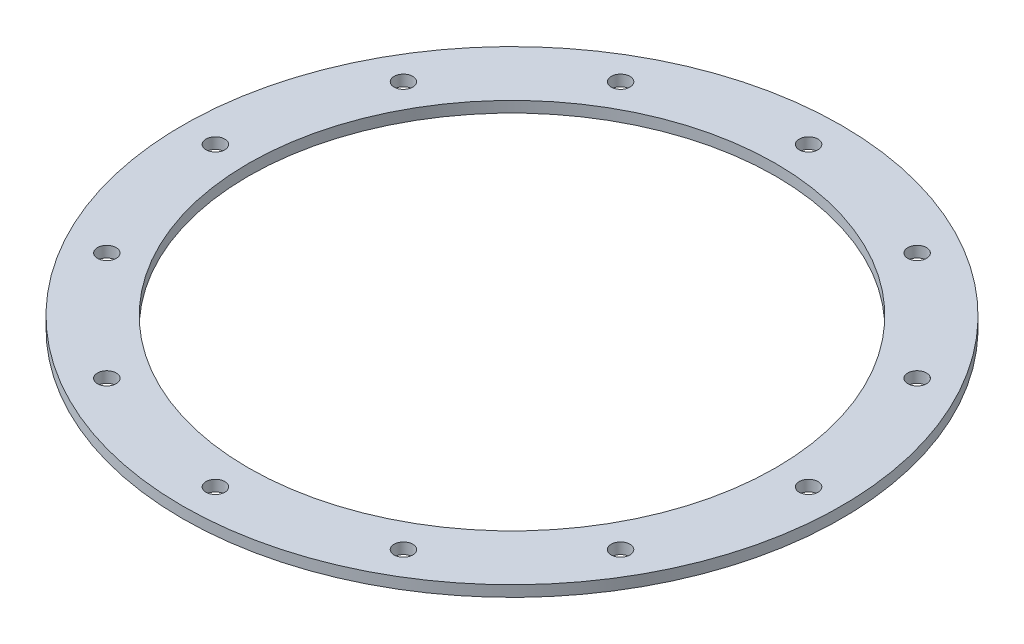
SolidWorks part; units mm, degrees
material "PTFE (general)"
ref_plane "Front Plane" through (0, 0, 0) normal (0, 0, 1) x (1, 0, 0)
ref_plane "Top Plane" through (0, 0, 0) normal (0, 1, 0) x (1, 0, 0)
ref_plane "Right Plane" through (0, 0, 0) normal (1, 0, 0) x (0, 0, -1)
ref_axis "Axis1" through (0, 55, 0) along (0, -1, 0)
sketch "Sketch1" plane through (0, 0, 0) normal (0, 0, 1) x (1, 0, 0)
  line L0 (-38.1, 0) -> (0, 0) construction
  line L1 (-38.1, 0) -> (-47.625, 0)
  line L2 (-38.1, 0) -> (-38.1, 1.5875)
  line L3 (-38.1, 1.5875) -> (-47.625, 1.5875)
  line L4 (-47.625, 0) -> (-47.625, 1.5875)
  line L7 (0, 1.5875) -> (-38.1, 1.5875) construction
  point P12 (-47.625, 0)
  point P18 (-38.1, 1.5875)
revolve "Main" add sketch "Sketch1" angle 360 about axis through (0, 55, 0) along (0, -1, 0)
sketch "Hole Location" plane through (0, 0, 0) normal (0, 1, 0) x (1, 0, 0)
  line L0 (0, 0) -> (-42.8625, 0) construction
  circle A0 centre (0, 0) radius 42.8625 construction
  dimension "D1" = 85.725
hole_wizard "#36 (0.1065) Diameter Hole1" positions "Sketch3" profile "Sketch5" hole size "#36" standard "ANSI Inch" end condition through all
sketch "Sketch3" plane through (0, 0, 0) normal (0, -1, 0) x (-1, 0, 0)
  point P0 (42.8625, 0)
sketch "Sketch5" plane through (-42.8625, 0, 0) normal (1, 0, 0) x (0, 0, -1)
  line L0 (0, 0) -> (0, 1.5875)
  line L1 (0, 1.5875) -> (1.3525, 1.5875)
  line L2 (1.3525, 1.5875) -> (1.3525, 0)
  line L5 (1.3525, 0) -> (0, 0)
  line L11 (0, -6.35) -> (0, 107.95) construction
  dimension "Thru Hole Dia." = 2.7051
  dimension "Thru Hole Depth" = 1.5875
pattern_circular "Screw Passthroughs" count 12 over 360 about axis through (0, 55, 0) along (0, -1, 0) of "#36 (0.1065) Diameter Hole1"
equation "\"D1@Hole Location\"=\"TANK DIAMETER@Cryo Tank.Assembly\"+\"GASKET SEAT THICKNESS@Cryo Tank.Assembly\""
